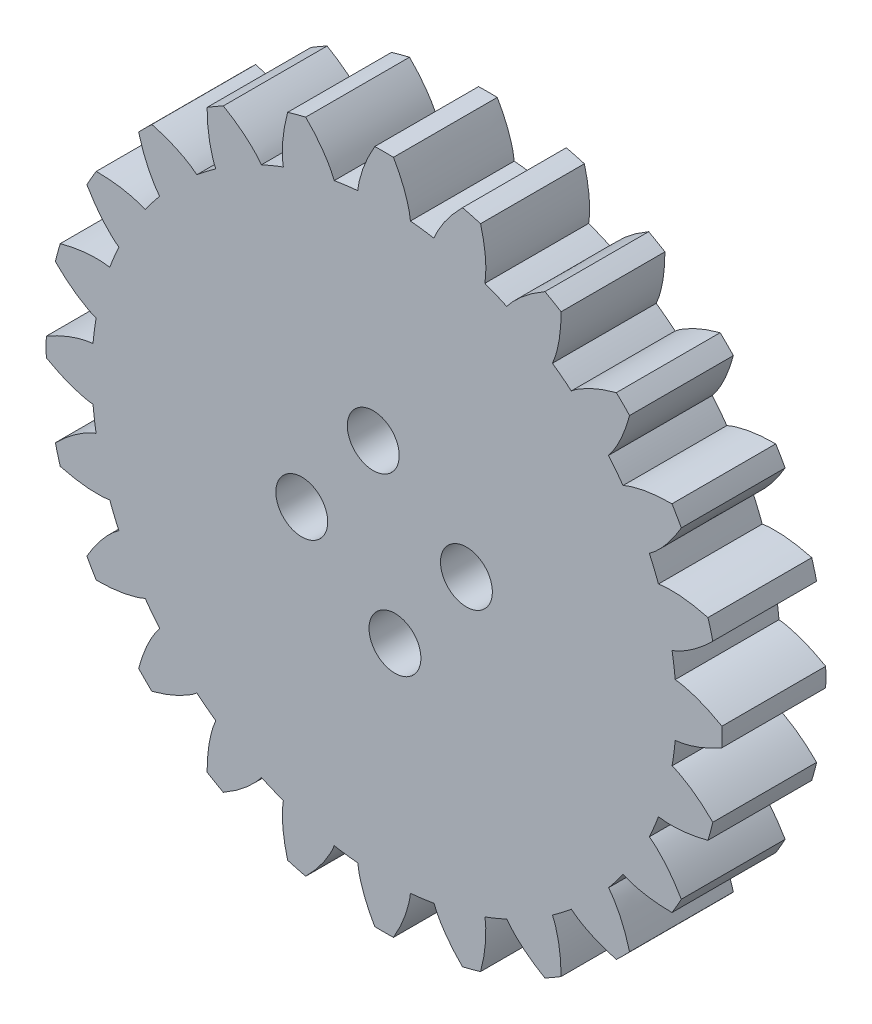
SolidWorks part; units mm, degrees
material "ABS"
ref_plane "Front Plane" through (0, 0, 0) normal (0, 0, 1) x (1, 0, 0)
ref_plane "Top Plane" through (0, 0, 0) normal (0, 1, 0) x (1, 0, 0)
ref_plane "Right Plane" through (0, 0, 0) normal (1, 0, 0) x (0, 0, -1)
sketch "Definition Drawing" plane through (0, 0, 0) normal (0, 0, 1) x (1, 0, 0)
  line L0 (16.2789, 0) -> (14.2789, 0) construction
  line L1 (0, 0) -> (-6.9516, 11.976) construction
  line L2 (0, 0) -> (0, 16.2789) construction
  line L3 (0, 0) -> (1.2743, 13.7886) construction
  line L4 (-6.9516, 11.976) -> (0.4506, 16.2726) construction
  line L5 (0, 0) -> (0.9494, 15.2493) construction
  line L6 (0, 0) -> (0.9993, 15.2462) construction
  line L7 (0, 0) -> (-5.0256, 12.9032) construction
  line L8 (-5.0256, 12.9032) -> (0.9558, 15.2329) construction
  line L9 (0, 0) -> (-2.9798, 13.5229) construction
  line L10 (-2.9798, 13.5229) -> (1.1993, 14.4438) construction
  line L11 (0, 0) -> (-0.8631, 13.8204) construction
  line L12 (-0.8631, 13.8204) -> (1.2725, 13.9538) construction
  circle A0 centre (0, 0) radius 13.8474 construction
  circle A1 centre (0, 0) radius 14.2789 construction
  circle A2 centre (0, 0) radius 15.2789 construction
  circle A3 centre (0, 0) radius 16.2789 construction
  circle A4 centre (0, 0) radius 14.0789 construction
  arc A5 (0.9494, 15.2493) -> (0.9993, 15.2462) centre (0, 0) cw construction
  spline S0 degree 3 poles (1.2743, 13.7886) (1.2817, 14.0092) (1.1458, 14.8862) (0.7794, 15.701) (0.4506, 16.2726) knots 0 0 0 0 0.250019 1 1 1 1 construction
  point P13 (15.2789, 0)
  dimension "D4" = 30.5577
  dimension "D5" = 27.6947
  dimension "D1" = 2
  dimension "D2" = 0.2
  dimension "D3" = 3.75
  dimension "D6" = 0.05
  dimension "D7" = 35.413
  dimension "D11" = 6.4191
  dimension "D12" = 4.2794
  dimension "D13" = 2.1397
  dimension "D8" = 26.56
  dimension "D9" = 17.707
  dimension "D10" = 8.853
sketch "Sketch5" plane through (0, 0, 0) normal (0, 0, 1) x (1, 0, 0)
  circle A1 centre (0, 0) radius 14.0789
  circle A2 centre (0, 0) radius 1.5
  circle A3 centre (0, 0) radius 14.0789 construction
  dimension "D1" = 3
extrude "Extrude Body" add sketch "Sketch5" along normal mid plane 5
sketch "Sketch6" plane through (0, 0, 0) normal (0, 0, 1) x (1, 0, 0)
  line L0 (0, 16.2789) -> (0, 0) construction
  line L4 (1.2743, 13.7886) -> (0.138, 1.4936)
  line L5 (0, 0) -> (1.2743, 13.7886) construction
  line L6 (-1.2743, 13.7886) -> (-0.138, 1.4936)
  arc A0 (0.4506, 16.2726) -> (-0.4506, 16.2726) centre (0, 0) ccw
  arc A3 (0.138, 1.4936) -> (-0.138, 1.4936) centre (0, 0) ccw
  circle A4 centre (0, 0) radius 1.5 construction
  spline S0 degree 3 poles (1.2743, 13.7886) (1.2817, 14.0092) (1.1458, 14.8862) (0.7794, 15.701) (0.4506, 16.2726) knots 0 0 0 0 0.250019 1 1 1 1
  spline S1 degree 3 poles (-1.2743, 13.7886) (-1.2817, 14.0092) (-1.1458, 14.8862) (-0.7794, 15.701) (-0.4506, 16.2726) knots 0 0 0 0 0.250019 1 1 1 1
extrude "Extrude Tooth" add sketch "Sketch6" along normal mid plane 5
pattern_circular "CirPattern1" count 24 over 360 about axis through (0, 0, 2.5) along (0, 0, -1) of "Extrude Tooth" reverse direction yes
sketch "Sketch8" plane through (0, 0, 0) normal (0, 0, 1) x (1, 0, 0)
  line L6 (0, 16.2789) -> (0, 0) construction
  line L7 (0, 0) -> (14.0979, -8.1394) construction
  line L8 (1.5, 9.7639) -> (1.5, 4.899)
  line L9 (4.9926, -1.1505) -> (9.2058, -3.5829)
  circle A2 centre (0, 0) radius 16.2789 construction
  arc A20 (10.6688, -2.9864) -> (2.748, 10.7326) centre (0, 0) ccw
  circle A21 centre (0, 0) radius 14.0789 construction
  arc A23 (9.2058, -3.5829) -> (10.6688, -2.9864) centre (9.7058, -2.7169) ccw
  arc A24 (4.9926, -1.1505) -> (4.494, -0.2327) centre (5.4926, -0.2844) cw
  arc A25 (1.5, 4.899) -> (2.0455, 4.0083) centre (2.5, 4.899) ccw
  arc A26 (1.5, 9.7639) -> (2.748, 10.7326) centre (2.5, 9.7639) cw
  arc A27 (4.494, -0.2327) -> (2.0455, 4.0083) centre (0, 0) ccw
  circle A28 centre (0, 0) radius 1.5 construction
  dimension "D1" = 3
  dimension "D6" = 1
  dimension "D4" = 3
  dimension "D5" = 3
  dimension "D2" = 3
  dimension "D3" = 120
extrude "Cut Spoke" cut sketch "Sketch8" against normal through all and the other way through all
pattern_circular "Pattern Spokes" count 3 over 360 about axis through (0, 0, 2.5) along (0, 0, -1) of "Cut Spoke"
scale "Scale1" scale about centroid uniform scaling yes scale factor 2
sketch "Sketch9" plane through (0, 0, 5) normal (0, 0, 1) x (1, 0, 0)
  circle A0 centre (0, 0) radius 24.5043
extrude "Boss-Extrude1" add sketch "Sketch9" against normal up to surface (10 mm away) up to face at (-10.0806, 5.82, -5)
sketch "Sketch10" plane through (0, 0, 5) normal (0, 0, 1) x (1, 0, 0)
  line L0 (0, 0) -> (22.2761, 0) construction
  line L1 (-7.9316, -1.0442) -> (7.9316, 1.0442) construction
  line L2 (-1.0442, 7.9316) -> (1.0442, -7.9316) construction
  circle A4 centre (-1.0442, 7.9316) radius 1.05
  circle A5 centre (7.9316, 1.0442) radius 1.05
  circle A6 centre (1.0442, -7.9316) radius 1.05
  circle A7 centre (-7.9316, -1.0442) radius 1.05
  dimension "D2" = 2.1
  dimension "D1" = 7.5
  dimension "D3" = 16
extrude "Cut-Extrude1" cut sketch "Sketch10" against normal up to next
sketch "Sketch11" plane through (0, 0, 5) normal (0, 0, 1) x (1, 0, 0)
  circle A0 centre (7.9316, 1.0442) radius 2.5
  circle A1 centre (-1.0442, 7.9316) radius 2.5
  circle A2 centre (1.0442, -7.9316) radius 2.5
  circle A3 centre (-7.9316, -1.0442) radius 2.5
  point P12 (0, 0)
  point P13 (-7.9316, -1.0442)
  dimension "D1" = 5
extrude "Cut-Extrude2" cut sketch "Sketch11" against normal offset from surface (8 mm away) 2 up to face at (8.9816, 1.0442, -5)
sketch "Sketch12" plane through (0, 0, 5) normal (0, 0, 1) x (1, 0, 0)
  circle A0 centre (0, 0) radius 1.6599
equation "\"nTeeth\"= 24"
equation "\"xThickness\"=5"
equation "\"dShaft\"= 3"
equation "\"aPressure\"=25"
equation "\"pitch\"= 4"
equation "\"rHeight\"= 2"
equation "\"rClearance\"= 0.2"
equation "\"xClearance\"=0.05"
equation "\"rFillet\"= 1"
equation "\"nSpokes\"= int ( ( \"nTeeth\" - 1 ) / 10 ) + 1'rounds up"
equation "\"dPitch\"= \"nTeeth\" * \"pitch\" / pi"
equation "\"xWall\"= IIF ( \"nTeeth\" > 30 , \"nTeeth\" / 10 , 3 )"
equation "\"dBase\"= \"dPitch\" * cos ( \"aPressure\" )"
equation "\"rOuter\"= \"dPitch\" / 2 + \"rHeight\" / 2"
equation "\"xInvolute\"= sqr ( \"rOuter\" ^ 2 - ( \"dBase\" / 2 ) ^ 2 )"
equation "\"aInvolute\"= 360 * \"xInvolute\" / ( \"dBase\" / 2 ) / 2 / pi"
equation "\"D1@Definition Drawing\" = \"rHeight\""
equation "\"D2@Definition Drawing\" = \"rClearance\""
equation "\"D4@Definition Drawing\" = \"dPitch\""
equation "\"D6@Definition Drawing\" = \"xClearance\""
equation "\"D5@Definition Drawing\" = \"dBase\""
equation "\"D7@Definition Drawing\" = \"aInvolute\""
equation "\"D11@Definition Drawing\" = \"xInvolute\" * 0.75"
equation "\"D12@Definition Drawing\" = \"xInvolute\" * 0.5"
equation "\"D13@Definition Drawing\" = \"xInvolute\" * 0.25"
equation "\"D8@Definition Drawing\" = \"aInvolute\" * 0.75"
equation "\"D9@Definition Drawing\" = \"aInvolute\" * 0.5"
equation "\"D10@Definition Drawing\" = \"aInvolute\" * 0.25"
equation "\"D1@Extrude Body\"=\"xThickness\""
equation "\"D1@Sketch5\"=\"dShaft\""
equation "\"D3@Definition Drawing\" = 360 / \"nTeeth\" / 2 / 2"
equation "\"D5@Sketch8\"=\"xWall\""
equation "\"D1@Sketch8\"=\"xWall\""
equation "\"D4@Sketch8\"=\"xWall\""
equation "\"D6@Sketch8\"=\"rFillet\""
equation "\"D1@Pattern Spokes\" = \"nSpokes\""
equation "\"rHub\"= IIF ( \"xWall\" * \"nSpokes\" / 6 > \"xWall\" , \"xWall\" * \"nSpokes\" / 6 , \"xWall\" )"
equation "\"D2@Sketch8\"=\"rHub\""
equation "\"D3@Sketch8\"=360/\"nSpokes\""
equation "\"D1@Extrude Tooth\" = \"xThickness\""
equation "\"D1@CirPattern1\"=\"nTeeth\""
